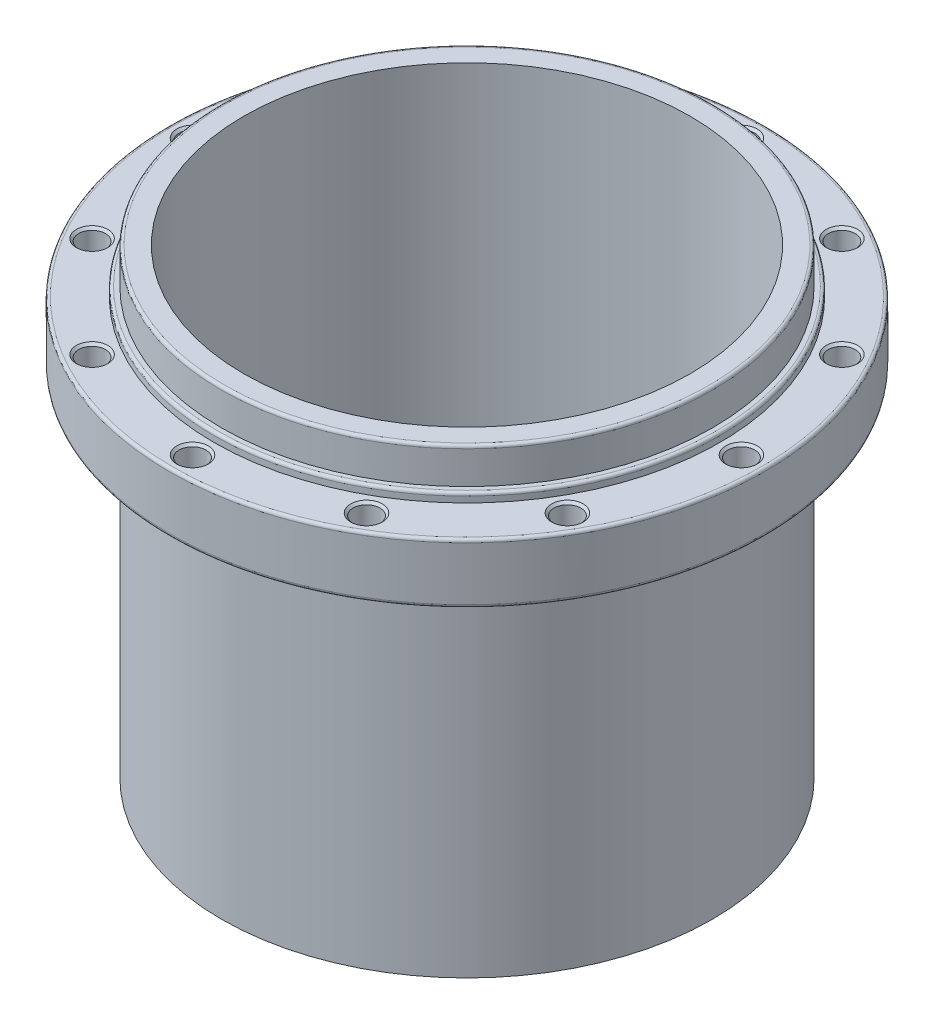
SolidWorks part; units mm, degrees
ref_plane "Front Plane" through (0, 0, 0) normal (0, 0, 1) x (1, 0, 0)
ref_plane "Top Plane" through (0, 0, 0) normal (0, 1, 0) x (1, 0, 0)
ref_plane "Right Plane" through (0, 0, 0) normal (1, 0, 0) x (0, 0, -1)
ref_axis "Axis1" through (0, 55, 0) along (0, -1, 0)
sketch "Sketch2" plane through (0, 0, 0) normal (0, 0, 1) x (1, 0, 0)
  line L0 (0, -54.3313) -> (-82.5, -54.3313)
  line L1 (0, 55) -> (0, -55) construction
  line L2 (-82.5, -54.3313) -> (-82.5, 65.6687)
  line L3 (0, 65.6687) -> (-82.5, 65.6687)
  line L4 (0, 65.6687) -> (0, -54.3313)
  line L5 (-82.5, 65.6687) -> (-100, 65.6687)
  line L6 (-100, 65.6687) -> (-100, 85.6687)
  line L7 (-100, 85.6687) -> (0, 85.6687)
  line L8 (0, 85.6687) -> (0, 65.6687)
  line L9 (-82.5, 85.6687) -> (-82.5, 100.6687)
  line L10 (-82.5, 100.6687) -> (0, 100.6687)
  line L11 (0, 100.6687) -> (0, 85.6687)
  line L12 (-85, 85.6687) -> (-85, 88.6687)
  line L13 (-85, 88.6687) -> (-82.5, 88.6687)
  line L14 (-85, 85.6687) -> (-82.5, 85.6687)
  line L15 (-82.5, 88.6687) -> (-82.5, 85.6687)
  dimension "D1" = 2.5
revolve "Revolve1" add sketch "Sketch2" angle 360 about axis through (0, 55, 0) along (0, -1, 0) region at (-41.25, 5.6687, 0) region at (-50, 75.6687, 0) region at (-41.25, 93.1687, 0)
sketch "Sketch3" plane through (0, 0, 0) normal (0, 0, 1) x (1, 0, 0)
  line L0 (0, -62.2986) -> (0, 118.8187)
  line L1 (0, 55) -> (0, -55) construction
  line L2 (0, -82.5) -> (0, 82.5) construction
  line L3 (0, 118.8187) -> (-75, 118.8187)
  line L4 (-75, 118.8187) -> (-75, -62.2986)
  line L5 (-75, -62.2986) -> (0, -62.2986)
revolve "Cut-Revolve2" cut sketch "Sketch3" angle 360 about axis through (0, 55, 0) along (0, -1, 0)
revolve "Revolve2" add sketch "Sketch2<3>" angle 360 about axis through (0, 55, 0) along (0, -1, 0) region at (-83.75, 87.1687, 0)
sketch "Sketch2<3>" plane through (0, 0, 0) normal (0, 0, 1) x (1, 0, 0) same geometry as "Sketch2"
sketch "Sketch6" plane through (0, 85.6687, 0) normal (0, 1, 0) x (1, 0, 0)
  circle A0 centre (0, 92.2346) radius 4.5
  circle A1 centre (46.1173, 79.8775) radius 4.5
  circle A2 centre (79.8775, 46.1173) radius 4.5
  circle A3 centre (92.2346, 0) radius 4.5
  circle A4 centre (79.8775, -46.1173) radius 4.5
  circle A5 centre (46.1173, -79.8775) radius 4.5
  circle A6 centre (0, -92.2346) radius 4.5
  circle A7 centre (-46.1173, -79.8775) radius 4.5
  circle A8 centre (-79.8775, -46.1173) radius 4.5
  circle A9 centre (-92.2346, 0) radius 4.5
  circle A10 centre (-79.8775, 46.1173) radius 4.5
  circle A11 centre (-46.1173, 79.8775) radius 4.5
  point P27 (0, 0)
  dimension "D1" = 12
  dimension "D2" = 9
extrude "Cut-Extrude1" cut sketch "Sketch6" against normal blind 40
chamfer "Chamfer1" distance 0.8 angle 45 12 edges at (-79.8775, 85.6687, 50.6173) (-46.1173, 85.6687, 84.3775) (0, 85.6687, 96.7346) (46.1173, 85.6687, 84.3775) (79.8775, 85.6687, 50.6173) (92.2346, 85.6687, 4.5) (79.8775, 85.6687, -41.6173) (46.1173, 85.6687, -75.3775) (0, 85.6687, -87.7346) (-46.1173, 85.6687, -75.3775) (-79.8775, 85.6687, -41.6173) (-92.2346, 85.6687, 4.5)
fillet "Fillet6" radius 1 2 edges at (0, 65.6687, 100) (0, 85.6687, 100) conic rho 0.5
fillet "Fillet8" radius 1 1 edges at (0, 88.6687, 85) conic rho 0.5
fillet "Fillet9" radius 1 1 edges at (0, 100.6687, 82.5) conic rho 0.5
